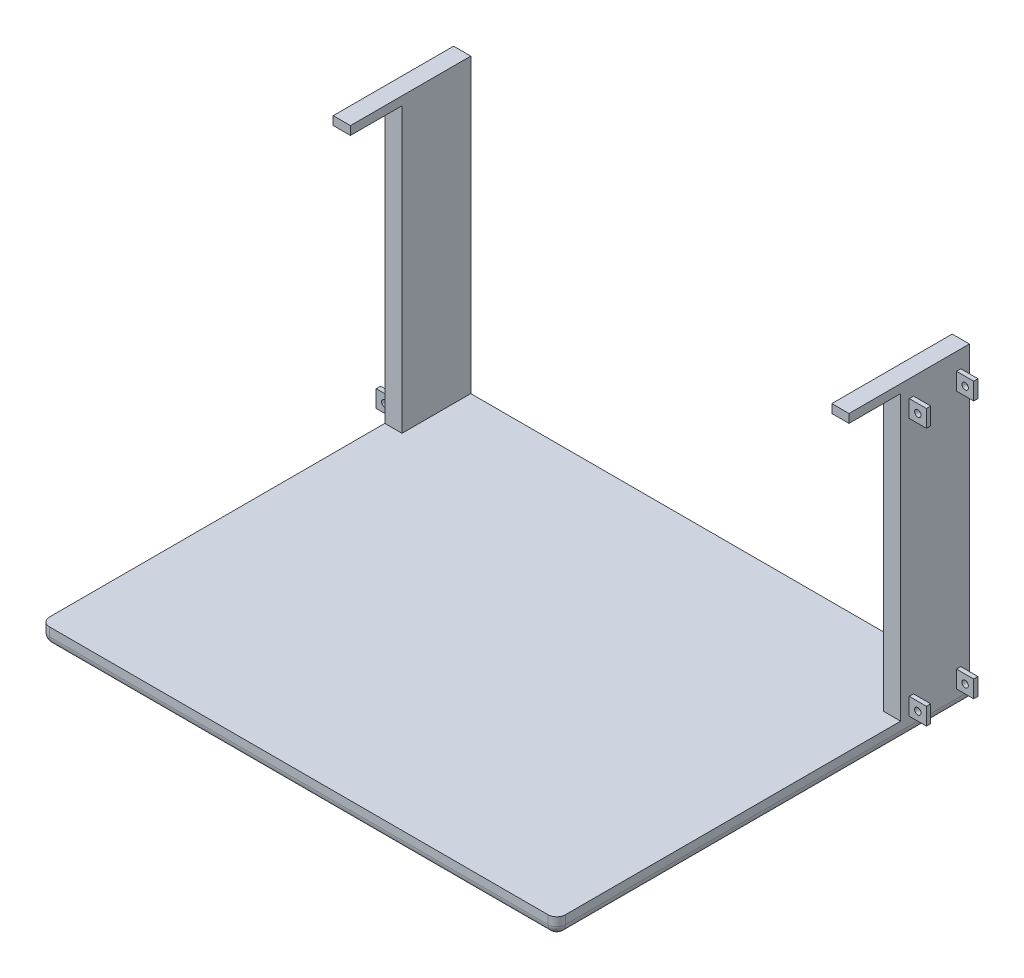
SolidWorks part; units mm, degrees
ref_plane "Front Plane" through (0, 0, 0) normal (0, 0, 1) x (1, 0, 0)
ref_plane "Top Plane" through (0, 0, 0) normal (0, 1, 0) x (1, 0, 0)
ref_plane "Right Plane" through (0, 0, 0) normal (1, 0, 0) x (0, 0, -1)
sketch "Sketch1" plane through (0, 0, 0) normal (0, 0, 1) x (1, 0, 0)
  line L0 (0, 0) -> (762, 0)
  line L1 (55, 0) -> (-55, 0) construction
  line L2 (762, 0) -> (762, 381)
  line L4 (762, 381) -> (0, 381)
  line L5 (762, 381) -> (762, 0)
  line L6 (762, 0) -> (0, 0)
  line L7 (0, 381) -> (0, 0)
  dimension "D1" = 762
  dimension "D2" = 381
extrude "Base Structure" add sketch "Sketch1" against normal blind 609.6 contours L4 L7 L0 L2 region at (381, 190.5, 0)
sketch "Sketch3" plane through (0, 0, -609.6) normal (0, 0, -1) x (-1, 0, 0)
  line L0 (335.28, 0) -> (-335.28, 0) construction
  line L1 (-736.6, 355.6) -> (-25.4, 355.6)
  line L2 (-736.6, 355.6) -> (-736.6, 25.4)
  line L3 (-736.6, 25.4) -> (-25.4, 25.4)
  line L4 (-25.4, 355.6) -> (-25.4, 25.4)
  line L5 (-762, 381) -> (0, 381) construction
  line L6 (-762, 0) -> (-762, 381) construction
  line L7 (0, 381) -> (0, 0) construction
  dimension "D1" = 25.4
  dimension "D2" = 25.4
  dimension "D3" = 25.4
  dimension "D4" = 25.4
extrude "Shell Cut" cut sketch "Sketch3" against normal blind 584.2
ref_plane "Mid Plane for Stability Holder" through (0, 0, -558.8) normal (0, 0, 1) x (1, 0, 0)
sketch "Sketch5" plane through (0, 0, -558.8) normal (0, 0, 1) x (1, 0, 0)
  line L0 (762, 0) -> (762, 381) construction
  line L1 (762, 355.6) -> (787.4, 355.6)
  line L2 (762, 355.6) -> (762, 330.2)
  line L3 (762, 330.2) -> (787.4, 330.2)
  line L4 (787.4, 355.6) -> (787.4, 330.2)
  line L5 (762, 381) -> (0, 381) construction
  circle A0 centre (774.7, 342.9) radius 4.7625
  dimension "D3" = 9.525
  dimension "D1" = 774.7
  dimension "D2" = 50.8
  dimension "D4" = 12.7
  dimension "D5" = 12.7
extrude "Stability Holder Cut for Top" add sketch "Sketch5" along normal mid plane 76.2
sketch "Sketch7" plane through (787.4, 0, 0) normal (1, 0, 0) x (0, 0, -1)
  line L0 (520.7, 355.6) -> (596.9, 355.6) construction
  line L1 (527.05, 355.6) -> (590.55, 355.6)
  line L2 (527.05, 355.6) -> (527.05, 330.2)
  line L3 (527.05, 330.2) -> (590.55, 330.2)
  line L4 (590.55, 355.6) -> (590.55, 330.2)
  line L5 (520.7, 330.2) -> (596.9, 330.2) construction
  line L6 (520.7, 330.2) -> (520.7, 355.6) construction
  line L7 (596.9, 330.2) -> (596.9, 355.6) construction
  dimension "D1" = 6.35
  dimension "D2" = 6.35
extrude "Insude Cut of Stability Holders" cut sketch "Sketch7" against normal blind 25.4
ref_plane "2Middle Plane For Chassis, Vertical" through (381, 0, 0) normal (1, 0, 0) x (0, 0, -1)
sketch "Sketch14" plane through (0, 0, -609.6) normal (0, 0, -1) x (-1, 0, 0)
  line L0 (-762, 381) -> (0, 381) construction
  line L1 (-25.4, 355.6) -> (-736.6, 355.6)
  line L2 (-25.4, 355.6) -> (-25.4, 381)
  line L3 (-25.4, 381) -> (-736.6, 381)
  line L4 (-736.6, 355.6) -> (-736.6, 381)
  line L5 (-736.6, 355.6) -> (-736.6, 25.4) construction
  dimension "D1" = 0
extrude "Top Shelling" cut sketch "Sketch14" against normal blind 406.4
sketch "Sketch16" plane through (0, 0, -609.6) normal (0, 0, -1) x (-1, 0, 0)
  line L0 (335.28, 0) -> (-335.28, 0) construction
  line L1 (-736.6, 25.4) -> (-25.4, 25.4)
  line L2 (-736.6, 25.4) -> (-736.6, 0)
  line L3 (-736.6, 0) -> (-25.4, 0)
  line L4 (-25.4, 25.4) -> (-25.4, 0)
  line L5 (-762, 0) -> (-762, 381) construction
  line L6 (-762, 0) -> (0, 0)
  line L7 (-762, 0) -> (-762, -76.2)
  line L8 (-762, -76.2) -> (0, -76.2)
  line L9 (0, 0) -> (0, -76.2)
  line L11 (-736.6, -50.8) -> (-25.4, -50.8)
  line L12 (-736.6, -50.8) -> (-736.6, 0)
  line L13 (-736.6, 0) -> (-25.4, 0)
  line L14 (-25.4, -50.8) -> (-25.4, 0)
  line M8 (-25.4, 25.4) -> (-736.6, 25.4)
  line M12 (-762, 0) -> (0, 0)
  dimension "D1" = 76.2
  dimension "D2" = 762
  dimension "D3" = 711.2
  dimension "D4" = 25.4
extrude "Bottom Extension" add sketch "Sketch16" against normal up to surface (609.6 mm away) contours L14 L11 L12 L7 L8 L9 M12 | L11 L14 L12 M12 region at (381, -59.0176, -609.6) region at (381, -25.4, -609.6) up to face at (381, 190.5, 0)
extrude "Bottom Shelling" cut sketch "Sketch16<6>" against normal blind 584.2 contours L4 L2 M8 M12 | L11 L14 L12 M12 region at (381, 12.7, -609.6) region at (381, -25.4, -609.6)
sketch "Sketch16<6>" plane through (0, 0, -609.6) normal (0, 0, -1) x (-1, 0, 0) same geometry as "Sketch16"
ref_plane "Plane4" through (0, 152.4, 0) normal (0, 1, 0) x (1, 0, 0)
mirror "Mirror5" about plane through (0, 152.4, 0) normal (0, 1, 0) of "Stability Holder Cut for Top"
sketch "Sketch17" plane through (787.4, 0, 0) normal (1, 0, 0) x (0, 0, -1)
  line L0 (520.7, -50.8) -> (596.9, -50.8) construction
  line L1 (520.7, -25.4) -> (527.05, -25.4)
  line L2 (520.7, -25.4) -> (520.7, -50.8)
  line L3 (520.7, -50.8) -> (527.05, -50.8)
  line L4 (527.05, -25.4) -> (527.05, -50.8)
  line L5 (520.7, -50.8) -> (596.9, -50.8) construction
  line L6 (596.9, -25.4) -> (590.55, -25.4)
  line L7 (596.9, -25.4) -> (596.9, -50.8)
  line L8 (596.9, -50.8) -> (590.55, -50.8)
  line L9 (590.55, -25.4) -> (590.55, -50.8)
  line L11 (527.05, -25.4) -> (590.55, -25.4)
  line L12 (527.05, -25.4) -> (527.05, -50.8)
  line L13 (527.05, -50.8) -> (590.55, -50.8)
  line L14 (590.55, -25.4) -> (590.55, -50.8)
  line M6 (596.9, -25.4) -> (520.7, -25.4)
  line M8 (520.7, -50.8) -> (596.9, -50.8)
  dimension "D1" = 6.35
  dimension "D2" = 6.35
extrude "Bottom Stabilty Holder Shell Cut" cut sketch "Sketch17" against normal up to surface (25.4 mm away) contours L9 L4 M6 M8 region at (787.4, -38.1, -558.8) up to face at (762, -38.1, -558.8)
sketch "Sketch18" plane through (762, 0, 0) normal (1, 0, 0) x (0, 0, -1)
  line L0 (0, 251.46) -> (0, -251.46) construction
  line L1 (0, -76.2) -> (609.6, -76.2) construction
  line L2 (0, -76.2) -> (0, 381) construction
  line L3 (609.6, -76.2) -> (609.6, 381) construction
  line L9 (609.6, 381) -> (0, 381) construction
  line L10 (508, -50.8) -> (0, -50.8)
  line L11 (508, -50.8) -> (508, 355.6)
  line L12 (508, 355.6) -> (0, 355.6)
  line L13 (0, -50.8) -> (0, 355.6)
  point P0 (0, 177.8)
  point P5 (0, -50.8)
  point P6 (508, -50.8)
  dimension "D1" = 254
  dimension "D2" = 25.4
  dimension "D3" = 101.6
  dimension "D4" = 25.4
  dimension "D5" = 25.4
  dimension "D6" = 0
extrude "3/4Shell Front Chassis Cut" cut sketch "Sketch18" against normal through all
ref_plane "Mid Plane For Chassis, Horizontal" through (0, 0, -12.7) normal (0, 0, 1) x (1, 0, 0)
sketch "Sketch19" plane through (0, 0, -12.7) normal (0, 0, 1) x (1, 0, 0)
  line L0 (749.3, -51.8465) -> (749.3, 25.2017)
  line L1 (673.1, 101.4017) -> (88.9, 101.4017)
  line L2 (12.7, 25.2017) -> (12.7, -51.8465)
  line L3 (762, -76.2) -> (762, -50.8) construction
  line L5 (0, -50.8) -> (0, -76.2) construction
  arc A0 (749.3, 25.2017) -> (673.1, 101.4017) centre (673.1, 25.2017) ccw
  arc A1 (12.7, 25.2017) -> (88.9, 101.4017) centre (88.9, 25.2017) cw
  dimension "D3" = 76.2
  dimension "D4" = 76.2
  dimension "D1" = 12.7
  dimension "D2" = 12.7
  dimension "D5" = 101.4017
  dimension "D6" = 51.8465
fillet "Fillet Corner of Front Chassis" radius 12.7 1 edges at (762, -63.5, 0)
ref_plane "Mid Plane of Wall" through (749.3, 0, 0) normal (1, 0, 0) x (0, 0, -1)
sketch "Sketch48" plane through (749.3, 0, 0) normal (1, 0, 0) x (0, 0, -1)
  line L0 (42.5652, 25.4) -> (520.7, 203.2)
  line L4 (12.7, -50.8) -> (508, -50.8) construction
  line L6 (12.7, -50.8) -> (508, -50.8) construction
  dimension "D1" = 76.2
  dimension "D3" = 254
  dimension "D4" = 42.5652
  dimension "D5" = 520.7
ref_plane "Mid Plane of Chassis, Vertical" through (508, 0, 0) normal (1, 0, 0) x (0, 0, -1)
sketch "Sketch68" plane through (508, 0, 0) normal (1, 0, 0) x (0, 0, -1)
  line L0 (15.24, 104.14) -> (317.5, 368.3)
  line L2 (203.2, 355.6) -> (203.2, 381) construction
  line L3 (508, 355.6) -> (0, 355.6) construction
  dimension "D1" = 15.24
  dimension "D2" = 114.3
  dimension "D3" = 12.7
  dimension "D4" = 104.14
sketch "Sketch87" plane through (508, 0, 0) normal (1, 0, 0) x (0, 0, -1)
  circle A0 centre (317.5, 368.3) radius 12.7
  dimension "D1" = 25.4
ref_plane "Plane for Steering Rack Holder" through (0, 368.3, 0) normal (0, 1, 0) x (1, 0, 0)
sketch "Sketch95" plane through (762, 0, 0) normal (1, 0, 0) x (0, 0, -1)
  line L0 (0, 251.46) -> (0, -251.46) construction
  line L1 (508, 355.6) -> (0, 355.6)
  line L2 (508, 355.6) -> (508, 381)
  line L3 (508, 381) -> (0, 381)
  line L4 (0, 355.6) -> (0, 381)
  line L5 (609.6, 381) -> (0, 381) construction
extrude "Cut Top Extrusion of Chassis" cut sketch "Sketch95" against normal through all
ref_plane "3Mid Plane of Chassis, Vertical" through (0, 0, -317.5) normal (0, 0, 1) x (1, 0, 0)
sketch "Sketch104" plane through (0, 0, -317.5) normal (0, 0, 1) x (1, 0, 0)
  line L0 (508, 368.3) -> (749.3, 368.3)
  line L1 (508, 355.6) -> (508, 381) construction
  line L2 (749.3, -251.46) -> (749.3, 251.46) construction
  line L3 (749.3, 368.3) -> (749.3, 127)
  line L4 (749.3, 25.4) -> (749.3, 203.2) construction
  line L5 (508, 368.3) -> (12.7, 368.3)
  line L6 (12.7, 368.3) -> (12.7, 127)
  dimension "D1" = 241.3
  dimension "D2" = 495.3
  dimension "D3" = 241.3
ref_plane "2Mid Plane Of wall, Vertical" through (749.3, 0, 0) normal (1, 0, 0) x (0, 0, -1)
sketch "Sketch118" plane through (749.3, 0, 0) normal (1, 0, 0) x (0, 0, -1)
  line L0 (317.5, 368.3) -> (508, 368.3)
  line L1 (508, -50.8) -> (508, 381) construction
  line L2 (13.97, 368.3) -> (-13.97, 368.3) construction
ref_plane "3Mid Plane Of wall, Vertical" through (762, 0, 0) normal (1, 0, 0) x (0, 0, -1)
sketch "Sketch171" plane through (762, 0, 0) normal (1, 0, 0) x (0, 0, -1)
  line L6 (508, 381) -> (431.7099, 381)
  line L7 (508, 381) -> (508, 368.3)
  line L8 (508, 368.3) -> (431.7099, 368.3)
  line L9 (431.7099, 381) -> (431.7099, 368.3)
  dimension "D1" = 12.7
  dimension "D2" = 76.2901
extrude "Extrusion of Steering Rack Holder" add sketch "Sketch171" against normal blind 25.4
sketch "Sketch172" plane through (0, 0, 0) normal (-1, 0, 0) x (0, 0, 1)
  line L1 (-508, 381) -> (-431.8, 381)
  line L2 (-508, 381) -> (-508, 368.3)
  line L3 (-508, 368.3) -> (-431.8, 368.3)
  line L4 (-431.8, 381) -> (-431.8, 368.3)
  dimension "D1" = 76.2
  dimension "D2" = 12.7
extrude "Extrusion of Other Steering Rack Holder" add sketch "Sketch172" against normal blind 25.4
mirror "Mirrors Stability Holders" about plane through (381, 0, 0) normal (1, 0, 0) of "Mirror5", "Stability Holder Cut for Top"
sketch "Sketch173" plane through (-25.4, 0, 0) normal (-1, 0, 0) x (0, 0, 1)
  line L0 (-520.7, 355.6) -> (-596.9, 355.6) construction
  line L1 (-590.55, 355.6) -> (-527.05, 355.6)
  line L2 (-590.55, 355.6) -> (-590.55, -50.8)
  line L3 (-590.55, -50.8) -> (-527.05, -50.8)
  line L4 (-527.05, 355.6) -> (-527.05, -50.8)
  line L5 (-520.7, -50.8) -> (-596.9, -50.8) construction
  line L6 (-596.9, 330.2) -> (-596.9, 355.6) construction
  line L7 (-520.7, -25.4) -> (-520.7, -50.8) construction
  dimension "D1" = 6.35
  dimension "D2" = 6.35
extrude "Extrusion of Other Stability Holders Top and Bottom" cut sketch "Sketch173" against normal up to surface (25.4 mm away) up to face at (0, 342.9, -558.8)
fillet "Fillet of Right Corner of Front Chassis" radius 12.7 1 edges at (0, -63.5, 0)
fillet "Fillet of Bottom Side of Front Chassis" radius 12.7 5 edges at (762, -76.2, -311.15) (758.2803, -76.2, -3.7197) (3.7197, -76.2, -3.7197) (381, -76.2, 0) (0, -76.2, -311.15)
ref_plane "Plane for Hollowing Diagonal/Middle Tube" through (508, 104.14, -15.24) normal (0, 0.6581, -0.753) x (-1, 0, 0)
sketch "Sketch205" plane through (508, 104.14, -15.24) normal (0, 0.6581, -0.753) x (-1, 0, 0)
  circle A0 centre (0, 0) radius 12.7
  circle A1 centre (0, 0) radius 8.7312
  circle A2 centre (239.522, 0) radius 12.7
  circle A3 centre (239.522, 0) radius 8.7313
  dimension "D1" = 25.4
  dimension "D2" = 17.4625
  dimension "D4" = 25.4
  dimension "D5" = 17.4625
  dimension "D3" = 239.522
ref_plane "Mid Plane of Front Tubing, Vertical" through (0, 0, -12.7) normal (0, 0, 1) x (1, 0, 0)
ref_plane "4Mid Plane of Wall, Vertical" through (749.3, 0, 0) normal (1, 0, 0) x (0, 0, -1)
sketch "Sketch266" plane through (749.3, 0, 0) normal (1, 0, 0) x (0, 0, -1)
  line L0 (12.7, 25.4) -> (508, 25.4)
  line L1 (12.7, 101.4017) -> (12.7, 25.2017) construction
  line L2 (12.7, 25.2017) -> (12.7, -51.8465) construction
  line L3 (508, -50.8) -> (508, 368.3) construction
  line L4 (62.7146, 25.4) -> (508, 199.7239)
  dimension "D1" = 25.4
  dimension "D2" = 62.7146
  dimension "D3" = 199.7239
sketch "Sketch267" plane through (0, 0, -12.7) normal (0, 0, 1) x (1, 0, 0)
  circle A0 centre (749.3, 25.2017) radius 8.7312
  circle A1 centre (749.3, 25.2017) radius 12.7
  dimension "D1" = 17.4625
  dimension "D2" = 25.4
sketch "Sketch268" plane through (0, -50.8, 0) normal (0, 1, 0) x (1, 0, 0)
  line L0 (673.1, 12.7) -> (749.3, 12.7) construction
  line L1 (749.3, -244.475) -> (749.3, 244.475) construction
  circle A0 centre (749.3, 12.7) radius 12.7
  circle A1 centre (749.3, 12.7) radius 8.7312
  dimension "D1" = 25.4
  dimension "D2" = 17.4625
ref_plane "Horizontal Plane, Circle for Horizontal Tubing" through (0, 127, 0) normal (0, -1, 0) x (-1, 0, 0)
sketch "Sketch271" plane through (0, 127, 0) normal (0, -1, 0) x (-1, 0, 0)
  circle A0 centre (-749.3, 317.5) radius 8.7312
  circle A1 centre (-749.3, 317.5) radius 12.7
  dimension "D1" = 17.4625
  dimension "D2" = 25.4
ref_plane "Plane Relative to Circle for Diagonal Tubing, Conn. Front" through (749.3, 25.4, -42.5652) normal (0, 0.3485, -0.9373) x (-1, 0, 0)
ref_plane "Vertical Plane to Circle, Steering Rack" through (749.3, 368.3, -317.5) normal (0, 0, -1) x (-1, 0, 0)
sketch "Sketch272" plane through (0, 0, -508) normal (0, 0, 1) x (1, 0, 0)
  line L0 (749.3, 368.3) -> (749.3, 127) construction
  line L2 (736.6, 368.3) -> (762, 368.3) construction
  circle A0 centre (749.3, 25.2017) radius 8.7312
  circle A1 centre (749.3, 355.6) radius 12.7
  circle A2 centre (749.3, 355.6) radius 8.7312
  dimension "D1" = 17.4625
  dimension "D2" = 25.4
  dimension "D3" = 17.4625
  dimension "D4" = 12.7
sketch "Sketch273" plane through (0, 0, -508) normal (0, 0, 1) x (1, 0, 0)
  line L2 (25.4, 368.3) -> (25.4, -50.8) construction
  line L3 (0, -50.8) -> (25.4, -50.8) construction
  circle A1 centre (12.7, 25.4) radius 12.7
  circle A2 centre (12.7, 25.4) radius 8.7312
  dimension "D1" = 12.7
  dimension "D3" = 25.4
  dimension "D4" = 17.4625
  dimension "D2" = 76.2
ref_plane "Plane5" through (12.7, 0, 0) normal (-1, 0, 0) x (0, 0, 1)
sketch "Sketch274" plane through (12.7, 0, 0) normal (-1, 0, 0) x (0, 0, 1)
  line L0 (-508, 199.7239) -> (-62.7146, 25.4)
sketch "Sketch276" plane through (0, 0, -508) normal (0, 0, 1) x (1, 0, 0)
  line L0 (12.7, 368.3) -> (12.7, 127) construction
  circle A0 centre (12.7, 355.6) radius 12.7
  circle A1 centre (12.7, 355.6) radius 8.7313
  dimension "D1" = 25.4
  dimension "D2" = 17.4625
  dimension "D3" = 12.7
